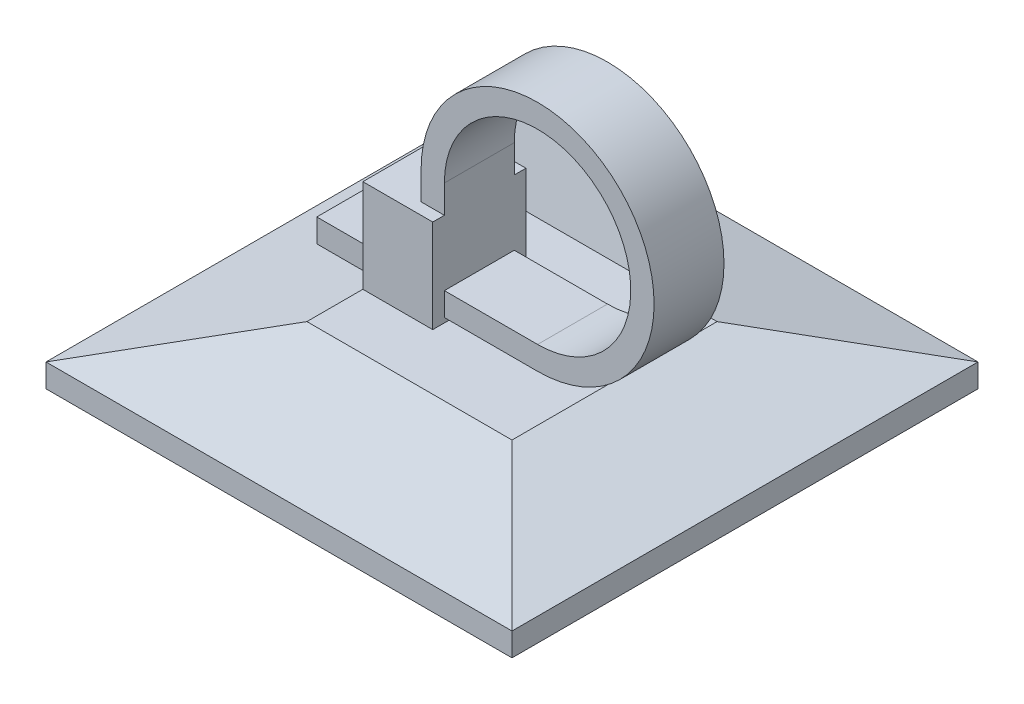
SolidWorks part; units mm, degrees
ref_plane "Front Plane" through (0, 0, 0) normal (0, 0, 1) x (1, 0, 0)
ref_plane "Top Plane" through (0, 0, 0) normal (0, 1, 0) x (1, 0, 0)
ref_plane "Right Plane" through (0, 0, 0) normal (1, 0, 0) x (0, 0, -1)
sketch "Sketch1" plane through (0, 0, 0) normal (0, 1, 0) x (1, 0, 0)
  line L0 (-10, -10) -> (10, 10) construction
  line L1 (-10, -10) -> (10, -10)
  line L2 (-10, -10) -> (-10, 10)
  line L3 (-10, 10) -> (10, 10)
  line L4 (10, -10) -> (10, 10)
  dimension "D1" = 20
extrude "Extrude1" add sketch "Sketch1" along normal blind 1
sketch "Sketch2" plane through (0, 1, 0) normal (0, 1, 0) x (-1, 0, 0)
  line L4 (10, -10) -> (10, 10)
  line L5 (10, 10) -> (-10, 10)
  line L6 (-10, 10) -> (-10, -10)
  line L7 (-10, -10) -> (10, -10)
  line L8 (10, -10) -> (10, 10)
  line L9 (10, 10) -> (-10, 10)
  line L10 (-10, 10) -> (-10, -10)
  line L11 (-10, -10) -> (10, -10)
  dimension "D1" = 0
extrude "Extrude2" add sketch "Sketch2" along normal blind 1.5 draft 75
sketch "Sketch3" plane through (0, 0, 0) normal (0, 0, 1) x (1, 0, 0)
  line L1 (-4.4019, 2.5) -> (-1.4019, 2.5)
  line L2 (-4.4019, 2.5) -> (-4.4019, 6.5)
  line L3 (-4.4019, 6.5) -> (-1.4019, 6.5)
  line L4 (-1.4019, 2.5) -> (-1.4019, 6.5)
  dimension "D1" = 4
  dimension "D2" = 3
extrude "Extrude3" add sketch "Sketch3" along normal mid plane 4
sketch "Sketch4" plane through (0, 0, 0) normal (0, 0, 1) x (1, 0, 0)
  line L0 (-1.4019, 2.5) -> (-1.4019, 6.5) construction
  line L1 (2.5981, 3.7) -> (-6.8786, 3.7)
  line L2 (-4.4019, 2.5) -> (4.4019, 2.5) construction
  line L3 (-1.4019, 6.5) -> (-1.4019, 7.7)
  arc A0 (-1.4019, 7.7) -> (2.5981, 3.7) centre (2.5981, 7.7) cw
  dimension "D2" = 8
  dimension "D1" = 1.2
extrude "Extrude-Thin1" add sketch "Sketch4" along normal mid plane 3 thin thin type one direction reverse wall 1
sketch "FilterSketch" plane through (0, 0, 0) normal (0, 0, 1) x (1, 0, 0)
  circle A0 centre (2.5981, 7.7) radius 2.95
  circle A1 centre (2.5981, 7.7) radius 2.95
  circle A2 centre (2.5981, 7.7) radius 2.95
  dimension "OuterDiameter" = 5.9
  dimension "NominalDiameter" = 5.9
  dimension "InnerDiameter" = 5.9
sketch3d "3DSketch1"
  arc A1 (-1.4019, 7.7, 1.5) -> (2.5981, 3.7, 1.5) centre (2.5981, 7.7, 1.5) ccw construction
  arc A2 (-1.4019, 7.7, -1.5) -> (2.5981, 3.7, -1.5) centre (2.5981, 7.7, -1.5) ccw construction
  point P0 (2.5981, 7.7, 1.5)
  point P1 (2.5981, 7.7, -1.5)
  point P5 (2.5981, 7.7, -5.5)
  point P9 (2.5981, 7.7, -2.5)
other "RPoint1"
ref_axis "Axis1" through (2.5981, 7.7, -3.5) along (0, 0, 1)
other "RPoint2"
ref_axis "Axis2" through (2.5981, 7.7, 3.5) along (0, 0, -1)
ref_axis "Clip Axis" through (2.5981, 7.7, 4.3871) along (0, 0, -1)
ref_axis "Axis of Rotation" through (0, 13.335, 0) along (0, -1, 0)
